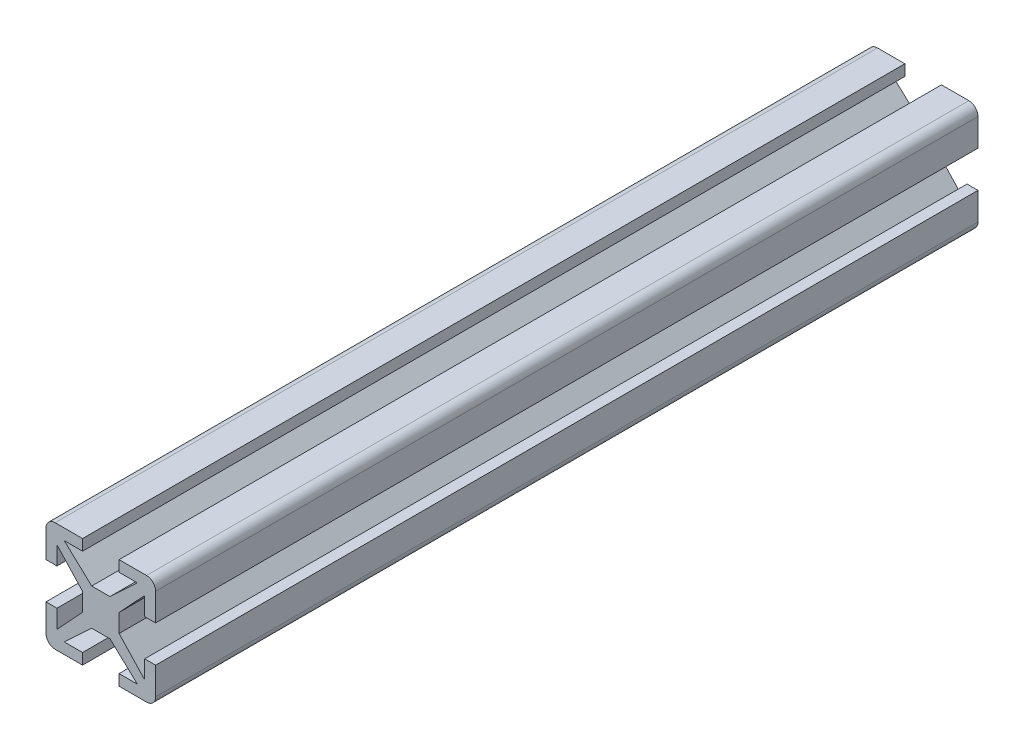
SolidWorks part; units mm, degrees
ref_plane "Plan de face" through (0, 0, 0) normal (0, 0, 1) x (1, 0, 0)
ref_plane "Plan de dessus" through (0, 0, 0) normal (0, 1, 0) x (1, 0, 0)
ref_plane "Plan de droite" through (0, 0, 0) normal (1, 0, 0) x (0, 0, -1)
sketch "Esquisse1" plane through (0, 0, 0) normal (0, 0, 1) x (1, 0, 0)
  line L0 (-6, 5) -> (-6, -5)
  line L1 (-5, 6) -> (5, 6)
  line L2 (-5, -6) -> (5, -6)
  line L3 (6, 5) -> (6, -5)
  line L4 (-5, 5) -> (5, -5) construction
  line L5 (5, 5) -> (-5, -5) construction
  arc A0 (-5, 6) -> (-6, 5) centre (-5, 5) ccw
  arc A1 (5, 6) -> (6, 5) centre (5, 5) cw
  arc A2 (6, -5) -> (5, -6) centre (5, -5) cw
  arc A3 (-5, -6) -> (-6, -5) centre (-5, -5) cw
  point P12 (0, 0)
  dimension "D1" = 1
  dimension "D2" = 1
  dimension "D4" = 1
  dimension "D3" = 12
extrude "Extrusion1" add sketch "Esquisse1" along normal mid plane 90
sketch "Esquisse3" plane through (0, 0, 45) normal (0, 0, 1) x (1, 0, 0)
  line L0 (6, 2) -> (4.8, 2)
  line L2 (4.8, 2) -> (4.8, 4)
  line L3 (2, 1) -> (2, -1)
  line L4 (4.8, -4) -> (4.8, -2)
  line L5 (4.8, -2) -> (6, -2)
  line L6 (6, -5) -> (6, 5) construction
  line L7 (4.8, 4) -> (2, 1)
  line L8 (6, 2) -> (6, -2)
  line L9 (4.8, -4) -> (2, -1)
  point P4 (6, 0)
  point P10 (6, 0)
  dimension "D1" = 4
  dimension "D2" = 1.2
  dimension "D3" = 4
  dimension "D4" = 2
  dimension "D5" = 2
extrude "Enlèv. mat.-Extru.1" cut sketch "Esquisse3" against normal through all
ref_axis "Axe1" through (0, 0, -1) along (0, 0, 1)
pattern_circular "Répétition circulaire1" count 4 every 90 about axis through (0, 0, -1) along (0, 0, 1) of "Enlèv. mat.-Extru.1"
